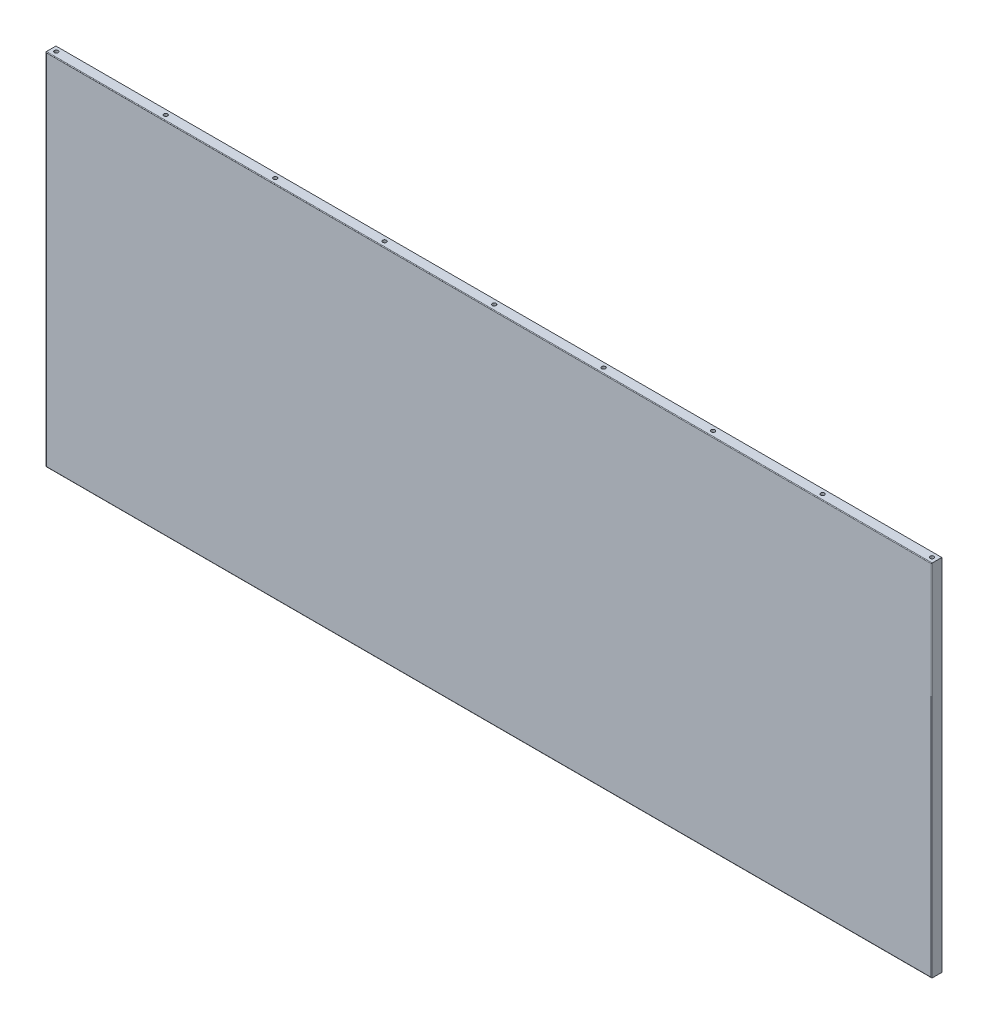
SolidWorks part; units mm, degrees
ref_plane "Front Plane" through (0, 0, 0) normal (0, 0, 1) x (1, 0, 0)
ref_plane "Top Plane" through (0, 0, 0) normal (0, 1, 0) x (1, 0, 0)
ref_plane "Right Plane" through (0, 0, 0) normal (1, 0, 0) x (0, 0, -1)
sketch "Sketch1" plane through (0, 0, 0) normal (0, 0, 1) x (1, 0, 0)
  line L1 (0, 0) -> (700, 0)
  line L2 (0, 0) -> (0, 284)
  line L3 (0, 284) -> (700, 284)
  line L4 (700, 0) -> (700, 284)
extrude "Boss-Extrude1" add sketch "Sketch1" along normal blind 8
fillet "Fillet1" radius 0.5 4 edges at (350, 284, 8) (700, 142, 8) (350, 0, 8) (0, 142, 8)
sketch "Sketch8" plane through (0, 284, 0) normal (0, 1, 0) x (1, 0, 0)
  line L0 (0, -7.5) -> (0, 0) construction
  circle A0 centre (4, -3.75) radius 1.5
  point P4 (0, -3.75)
  dimension "D1" = 4
extrude "Cut-Extrude6" cut sketch "Sketch8" against normal blind 20
ref_axis "Axis1" through (699.5, 142, 8) along (-1, 0, 0)
ref_plane "Plane1" through (0, 142, 0) normal (0, 1, 0) x (-1, 0, 0)
pattern_linear "LPattern4" count 9 spacing 86.5 along (1, 0, 0) of "Cut-Extrude6"
mirror "Mirror1" about plane through (0, 142, 0) normal (0, 1, 0) of "LPattern4", "Cut-Extrude6"
